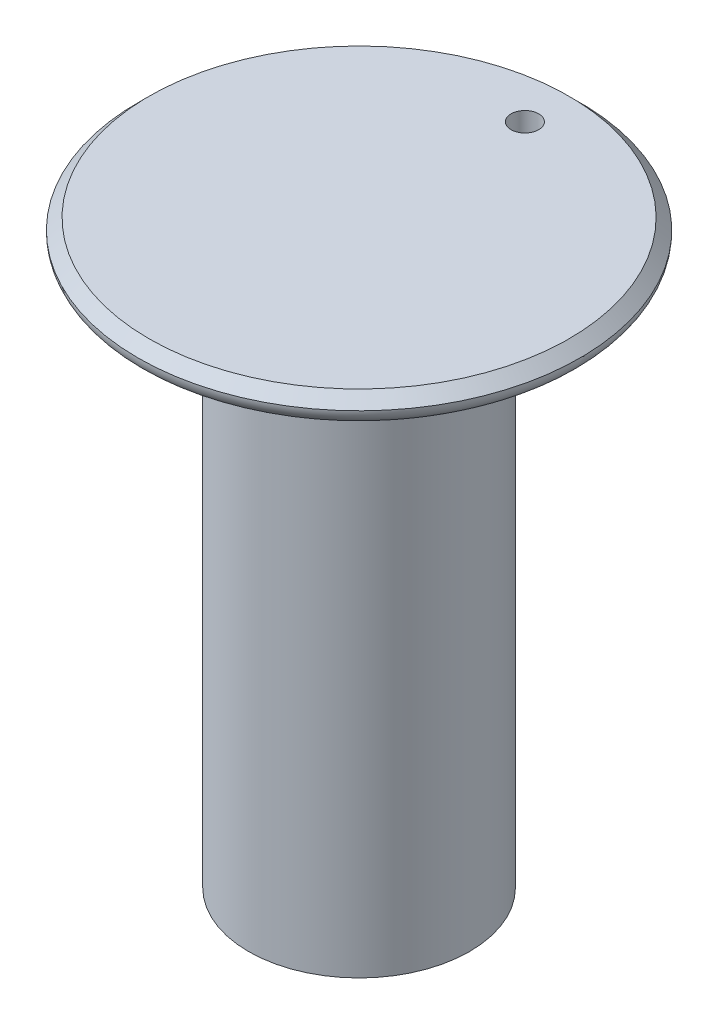
SolidWorks part; units mm, degrees
ref_plane "Front Plane" through (0, 0, 0) normal (0, 0, 1) x (1, 0, 0)
ref_plane "Top Plane" through (0, 0, 0) normal (0, 1, 0) x (1, 0, 0)
ref_plane "Right Plane" through (0, 0, 0) normal (1, 0, 0) x (0, 0, -1)
sketch "Sketch1" plane through (0, 0, 0) normal (0, 1, 0) x (1, 0, 0)
  circle A0 centre (0, 0) radius 20
  dimension "D1" = 40
extrude "Boss-Extrude1" add sketch "Sketch1" along normal mid plane 100
ref_plane "Plane1" through (0, 50, 0) normal (0, 1, 0) x (1, 0, 0)
sketch "Sketch3" plane through (0, 50, 0) normal (0, 1, 0) x (1, 0, 0)
  circle A0 centre (0, 0) radius 40
  dimension "D1" = 80
extrude "Boss-Extrude2" add sketch "Sketch3" along normal blind 5
chamfer "Chamfer1" distance 2 angle 45 1 edges at (0, 55, 40)
sketch "Sketch4" plane through (0, 55, 0) normal (0, 1, 0) x (1, 0, 0)
  line L0 (0, 40) -> (0, 20) construction
  line L1 (0, -20) -> (0, -40) construction
  line L2 (-30.7164, 25.6223) -> (30.7164, -25.6223) construction
  line L3 (-33.3329, -22.1114) -> (33.3329, 22.1114) construction
  circle A1 centre (0, 30) radius 2.5
  circle A2 centre (0, 0) radius 40 construction
  circle A3 centre (0, 0) radius 20 construction
  dimension "D1" = 5
extrude "Cut-Extrude1" cut sketch "Sketch4" against normal through all both and the other way through all
fillet "Fillet1" radius 3 1 edges at (0, 50, 40)
